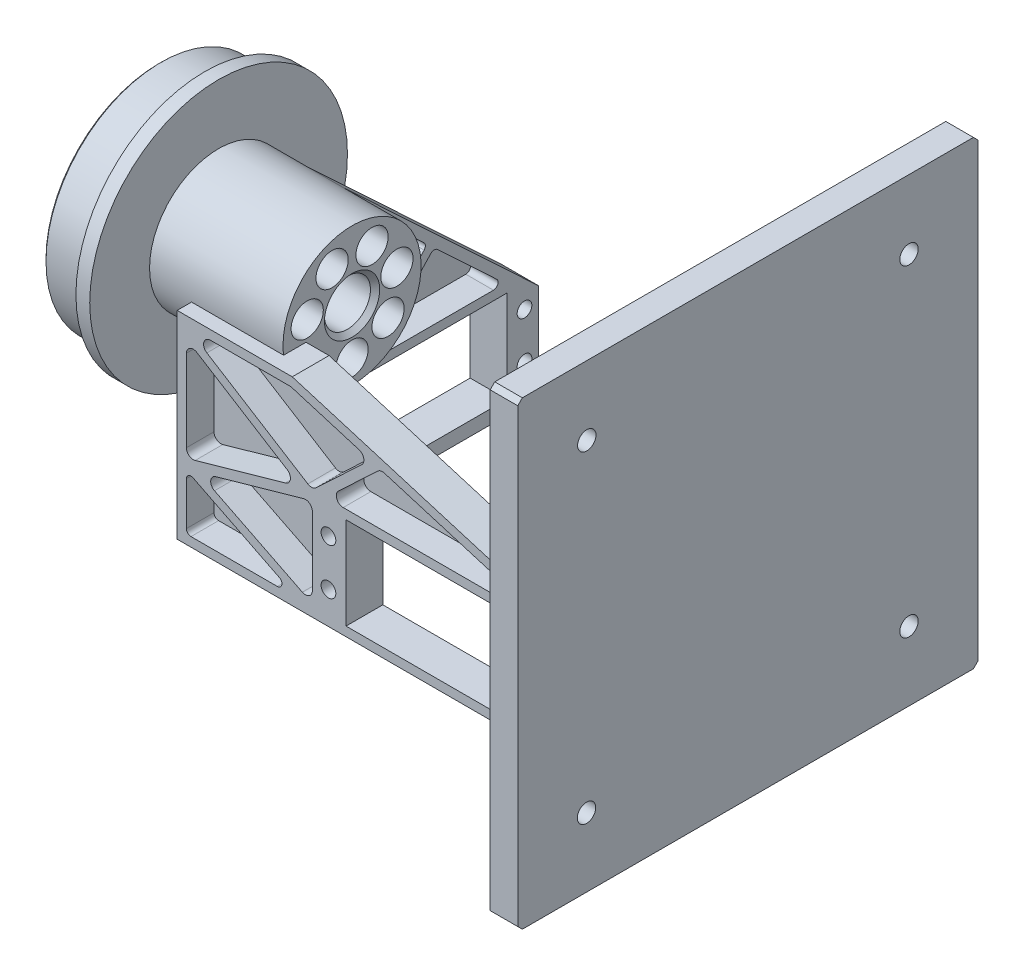
SolidWorks part; units mm, degrees
ref_plane "前视基准面" through (0, 0, 0) normal (0, 0, 1) x (1, 0, 0)
ref_plane "上视基准面" through (0, 0, 0) normal (0, 1, 0) x (1, 0, 0)
ref_plane "右视基准面" through (0, 0, 0) normal (1, 0, 0) x (0, 0, -1)
sketch "草图1" plane through (0, 0, 0) normal (0, 0, 1) x (1, 0, 0)
  line L0 (0, 42.2306) -> (0, 0) construction
  line L1 (0, 0) -> (67.1021, 0) construction
  line L2 (0, 28) -> (3, 28)
  line L3 (3, 28) -> (3, 25)
  line L4 (3, 25) -> (13, 25)
  line L5 (13, 25) -> (13, 28)
  line L6 (13, 28) -> (16, 28)
  line L7 (16, 28) -> (16, 15)
  line L8 (16, 15) -> (45, 15)
  line L9 (45, 15) -> (45, 5)
  line L10 (45, 5) -> (7.5, 5)
  line L11 (0, 12.5) -> (0, 28)
  line L12 (7.5, 5) -> (0, 12.5)
  dimension "D1" = 10
  dimension "D2" = 10
  dimension "D3" = 50
  dimension "D4" = 3
  dimension "D5" = 10
  dimension "D6" = 3
  dimension "D7" = 45
  dimension "D8" = 45
  dimension "D9" = 25
revolve "旋转1" add sketch "草图1" angle 360 about L1
ref_plane "基准面1" through (26, 0, 0) normal (1, 0, 0) x (0, 0, -1)
sketch "草图2" plane through (26, 0, 0) normal (1, 0, 0) x (0, 0, -1)
  line L0 (0, 0) -> (0, 50) construction
  line L1 (-13.9972, 50.28) -> (-14.997, 0.3)
  line L2 (13.9972, 50.28) -> (14.997, 0.3)
  circle A0 centre (0, 0) radius 5 construction
  circle A1 centre (0, 0) radius 5
  circle A2 centre (0, 0) radius 15 construction
  arc A3 (-14.997, 0.3) -> (14.997, 0.3) centre (0, 0) ccw
  circle A4 centre (0, 50) radius 6.5
  circle A5 centre (0, 50) radius 9.5 construction
  arc A6 (13.9972, 50.28) -> (-13.9972, 50.28) centre (0, 50) ccw
  circle A7 centre (0, 59.5) radius 1.5
  circle A8 centre (8.2272, 54.75) radius 1.5
  circle A9 centre (8.2272, 45.25) radius 1.5
  circle A10 centre (0, 40.5) radius 1.5
  circle A11 centre (-8.2272, 45.25) radius 1.5
  circle A12 centre (-8.2272, 54.75) radius 1.5
  point P26 (0, 50)
  dimension "D1" = 13
  dimension "D2" = 19
  dimension "D3" = 28
  dimension "D5" = 3
  dimension "D4" = 50
  dimension "D6" = 6
extrude "凸台-拉伸1" add sketch "草图2" along normal blind 8
sketch "草图3" plane through (34, 0, 0) normal (1, 0, 0) x (0, 0, -1)
  line L11 (13.4973, 0.27) -> (12.4975, 50.25)
  line L12 (13.3665, 6.807) -> (13.0385, 23.2073)
  line L13 (0, 15) -> (0, 50) construction
  line L14 (-12.4975, 50.25) -> (-13.4973, 0.27)
  line L15 (-12.6236, 43.9465) -> (-12.9969, 25.2871)
  line L16 (2.5, 14.7902) -> (12.9969, 25.2871)
  line L17 (13.0385, 23.2073) -> (4.2241, 14.393)
  line L18 (-2.5, 14.7902) -> (-12.9969, 25.2871)
  line L19 (-13.0385, 23.2073) -> (-4.2241, 14.393)
  line L20 (12.9969, 25.2871) -> (12.6236, 43.9465)
  line L21 (-13.0385, 23.2073) -> (-13.3665, 6.807)
  circle A10 centre (0, 50) radius 12.5
  arc A11 (14.997, 0.3) -> (-14.997, 0.3) centre (0, 0) ccw construction
  arc A12 (13.3665, 6.807) -> (4.2241, 14.393) centre (0, 0) ccw
  arc A13 (-12.6236, 43.9465) -> (12.6236, 43.9465) centre (0, 50) ccw
  arc A14 (13.9972, 50.28) -> (-13.9972, 50.28) centre (0, 50) ccw construction
  arc A15 (2.5, 14.7902) -> (-2.5, 14.7902) centre (0, 0) ccw
  arc A16 (-4.2241, 14.393) -> (-13.3665, 6.807) centre (0, 0) ccw
  dimension "D1" = 25
  dimension "D4" = 1.5
  dimension "D2" = 1.5
  dimension "D5" = 90
  dimension "D6" = 5
  dimension "D3" = 1.5
extrude "切除-拉伸1" cut sketch "草图3" against normal blind 6
fillet "圆角1" radius 1.5 12 edges at (31, 25.2871, -12.9969) (31, 43.9465, -12.6236) (31, 43.9465, 12.6236) (31, 14.7902, 2.5) (31, 14.393, 4.2241) (31, 23.2073, 13.0385) (31, 6.807, 13.3665) (31, 6.807, -13.3665) (31, 23.2073, -13.0385) (31, 14.393, -4.2241) (31, 14.7902, -2.5) (31, 25.2871, 12.9969)
sketch "草图4" plane through (45, 0, 0) normal (1, 0, 0) x (0, 0, -1)
  line L0 (-10, -1.9376) -> (-10, -45)
  line L1 (-10, -45) -> (-18, -45)
  line L2 (-18, -45) -> (-18, -1.9376)
  line L3 (-18, -1.9376) -> (-10, -1.9376)
  circle A0 centre (0, 0) radius 15 construction
  circle A2 centre (0, 0) radius 5 construction
  dimension "D1" = 10
  dimension "D2" = 45
  dimension "D3" = 8
extrude "凸台-拉伸2" add sketch "草图4" along normal blind 65 and the other way blind 20
sketch "草图5" plane through (0, 0, 18) normal (0, 0, 1) x (1, 0, 0)
  line L0 (0, 0) -> (152.7584, 0) construction
  line L1 (57.87, -38) -> (106.5, -38) construction
  line L2 (57.87, -38) -> (57.87, -28) construction
  line L3 (57.87, -28) -> (106.5, -28) construction
  line L4 (106.5, -38) -> (106.5, -28) construction
  line L5 (57.87, -38) -> (106.5, -28) construction
  line L6 (57.87, -28) -> (106.5, -38) construction
  line L8 (25, -45) -> (110, -45) construction
  line L9 (61.685, -43) -> (102.685, -43)
  line L10 (61.685, -43) -> (61.685, -23)
  line L11 (61.685, -23) -> (102.685, -23)
  line L12 (102.685, -43) -> (102.685, -23)
  line L13 (61.685, -43) -> (102.685, -23) construction
  line L14 (61.685, -23) -> (102.685, -43) construction
  line L15 (110, -1.9376) -> (110, -45) construction
  circle A0 centre (106.5, -28) radius 1.6
  circle A1 centre (106.5, -38) radius 1.6
  circle A2 centre (57.87, -28) radius 1.6
  circle A3 centre (57.87, -38) radius 1.6
  point P0 (82.185, -33)
  point P14 (82.185, -33)
  dimension "D3" = 3.2
  dimension "D5" = 3.5
  dimension "D1" = 10
  dimension "D2" = 48.63
  dimension "D4" = 12
  dimension "D6" = 20
  dimension "D7" = 41
extrude "切除-拉伸2" cut sketch "草图5" against normal through all
sketch "草图6" plane through (0, 0, 18) normal (0, 0, 1) x (1, 0, 0)
  line L0 (50, -1.9376) -> (110, -20)
  line L1 (25, -1.9376) -> (110, -1.9376) construction
  line L3 (110, -1.9376) -> (110, -45) construction
  line L4 (110, -20) -> (110, -1.9376)
  line L5 (110, -1.9376) -> (50, -1.9376)
  line L6 (25, -30) -> (55, -45)
  line L7 (25, -1.9376) -> (25, -45) construction
  line L8 (25, -45) -> (110, -45) construction
  line L9 (55, -45) -> (25, -45)
  line L10 (25, -45) -> (25, -30)
  dimension "D1" = 25
  dimension "D2" = 60
  dimension "D3" = 30
  dimension "D4" = 15
extrude "切除-拉伸3" cut sketch "草图6" against normal through all
sketch "草图7" plane through (0, 0, 18) normal (0, 0, 1) x (1, 0, 0)
  line L6 (106.3837, -21) -> (54.37, -21)
  line L7 (54.37, -21) -> (54.37, -42.4489)
  line L8 (102.685, -23) -> (61.685, -23) construction
  line L9 (49.7055, -3.9376) -> (27, -3.9376)
  line L10 (49.7055, -3.9376) -> (27, -3.9376)
  line L12 (108, -21.4866) -> (49.7055, -3.9376)
  line L14 (27, -3.9376) -> (27, -28.7639)
  line L15 (27, -28.7639) -> (55.4721, -43)
  line L16 (55.4721, -43) -> (108, -43)
  line L17 (108, -43) -> (108, -21.4866)
  line L18 (106.3837, -21) -> (49.7055, -3.9376)
  line L20 (27, -3.9376) -> (27, -28.7639)
  line L21 (27, -28.7639) -> (54.37, -42.4489)
  circle A0 centre (57.87, -28) radius 1.6 construction
  dimension "D2" = 3.5
  dimension "D3" = 2
  dimension "D1" = 2
extrude "切除-拉伸4" cut sketch "草图7" against normal blind 6
sketch "草图8" plane through (0, 0, 12) normal (0, 0, 1) x (1, 0, 0)
  line L0 (54.37, -21) -> (27, -3.9376) construction
  line L1 (54.37, -21) -> (27, -28.7639) construction
  line L2 (54.37, -21) -> (66.9811, -9.1383) construction
  line L3 (106.3837, -21) -> (49.7055, -3.9376) construction
  line L4 (66.9811, -9.1383) -> (54.37, -21)
  line L6 (54.37, -21) -> (106.3837, -21) construction
  line L7 (57.2891, -21) -> (69.1925, -9.804)
  line L8 (69.1925, -9.804) -> (66.9811, -9.1383)
  line L9 (54.37, -21) -> (27, -3.9376)
  line L10 (27, -3.9376) -> (27, -6.2944)
  line L11 (27, -3.9376) -> (27, -28.7639) construction
  line L12 (27, -6.2944) -> (51.7717, -21.737)
  line L15 (27, -28.7639) -> (51.7717, -21.737)
  line L17 (54.37, -42.4489) -> (54.37, -21) construction
  line L18 (54.37, -23.0789) -> (57.2891, -21)
  line L19 (27, -28.7639) -> (29.6528, -30.0903)
  line L20 (27, -28.7639) -> (54.37, -42.4489) construction
  line L21 (29.6528, -30.0903) -> (54.37, -23.0789)
  dimension "D1" = 60
  dimension "D2" = 2
  dimension "D3" = 2
  dimension "D4" = 2
extrude "凸台-拉伸3" add sketch "草图8" along normal up to surface (6 mm away) up to face at (53.1382, -20.1814, 18)
fillet "圆角2" radius 1.5 13 edges at (27, -6.2944, 15) (106.3837, -21, 15) (69.1925, -9.804, 15) (49.7055, -3.9376, 15) (27, -3.9376, 15) (54.37, -21, 15) (66.9811, -9.1383, 15) (54.37, -42.4489, 15) (57.2891, -21, 15) (27, -28.7639, 15) (51.7717, -21.737, 15) (29.6528, -30.0903, 15) (54.37, -23.0789, 15)
chamfer "倒角1" distance 5 angle 45 1 edges at (35, -11.1803, 10) first distance on face at (58.125, -20.7795, 10)
sketch "草图10" plane through (0, 0, 0) normal (-1, 0, 0) x (0, 0, 1)
  circle A0 centre (0, 0) radius 21 construction
  circle A1 centre (0, 21) radius 2.5
  circle A2 centre (18.1865, -10.5) radius 2.5
  circle A3 centre (-18.1865, -10.5) radius 2.5
  point P11 (0, 0)
  dimension "D1" = 42
  dimension "D2" = 5
  dimension "D3" = 3
extrude "切除-拉伸6" cut sketch "草图10" against normal blind 10
sketch "草图9" plane through (0, 0, 0) normal (-1, 0, 0) x (0, 0, 1)
  circle A0 centre (0, 0) radius 16
  circle A2 centre (0, 0) radius 28
  circle A3 centre (0, 0) radius 28
  dimension "D1" = 32
  dimension "D2" = 0
extrude "切除-拉伸5" cut sketch "草图9" against normal up to surface (3 mm away) up to face at (3, 0, 28)
chamfer "倒角2" distance 0.5 angle 45 5 edges at (0, 0, 16) (3, 0, 25) (3, -10.5, -15.6865) (3, -10.5, 20.6865) (3, 21, 2.5)
sketch "草图11" [suppressed] plane through (3, 0, 0) normal (-1, 0, 0) x (0, 0, 1)
  circle A0 centre (0, 0) radius 67.9276
extrude "切除-拉伸7" [suppressed] cut sketch "草图11" against normal through all
sketch "草图12" [suppressed] plane through (3, 0, 0) normal (1, 0, 0) x (0, 0, -1)
  circle A0 centre (0, 21) radius 2.5 construction
  circle A1 centre (0, 21) radius 2.5
  circle A2 centre (0, 21) radius 1.6
  circle A3 centre (18.1865, -10.5) radius 2.5
  circle A4 centre (18.1865, -10.5) radius 1.6
  circle A5 centre (-18.1865, -10.5) radius 2.5
  circle A6 centre (-18.1865, -10.5) radius 1.6
  point P12 (0, 0)
  dimension "D1" = 3.2
  dimension "D2" = 3
extrude "凸台-拉伸4" [suppressed] add sketch "草图12" against normal blind 3
sketch "草图13" [suppressed] plane through (3, 0, 0) normal (1, 0, 0) x (0, 0, -1)
  line L0 (0, 0) -> (0, 29.2927) construction
  arc A0 (-2.9985, 21.0938) -> (-2.462, 19.2857) centre (0, 21) ccw
  arc A1 (-2.462, 19.2857) -> (-3.1098, 17.7293) centre (-3.2826, 18.7143) cw
  arc A2 (15.4709, -11.775) -> (13.7991, -11.5579) centre (14.5657, -12.2) ccw
  circle A3 centre (0, 0) radius 22.5
  arc A4 (-4.184, 22.1076) -> (-21.2377, -7.4303) centre (0, 0) ccw
  arc A5 (2.462, 19.2857) -> (2.9985, 21.0938) centre (0, 21) ccw
  circle A6 centre (0, 0) radius 18
  arc A7 (-3.1098, 17.7293) -> (-16.909, -6.1715) centre (0, 0) ccw
  arc A8 (2.462, 19.2857) -> (3.1098, 17.7293) centre (3.2826, 18.7143) ccw
  arc A9 (15.4709, -11.775) -> (16.7685, -13.1437) centre (18.1865, -10.5) ccw
  arc A10 (19.767, -7.9501) -> (17.9329, -7.5107) centre (18.1865, -10.5) ccw
  arc A11 (17.9329, -7.5107) -> (16.909, -6.1715) centre (17.8484, -6.5143) cw
  arc A12 (-17.9329, -7.5107) -> (-16.909, -6.1715) centre (-17.8484, -6.5143) ccw
  arc A13 (-17.9329, -7.5107) -> (-19.767, -7.9501) centre (-18.1865, -10.5) ccw
  arc A14 (-16.7685, -13.1437) -> (-15.4709, -11.775) centre (-18.1865, -10.5) ccw
  arc A15 (-15.4709, -11.775) -> (-13.7991, -11.5579) centre (-14.5657, -12.2) cw
  arc A16 (16.909, -6.1715) -> (3.1098, 17.7293) centre (0, 0) ccw
  arc A17 (21.2377, -7.4303) -> (4.184, 22.1076) centre (0, 0) ccw
  arc A18 (-13.7991, -11.5579) -> (13.7991, -11.5579) centre (0, 0) ccw
  arc A19 (-17.0537, -14.6772) -> (17.0537, -14.6772) centre (0, 0) ccw
  arc A20 (4.184, 22.1076) -> (2.9985, 21.0938) centre (3.998, 21.125) ccw
  arc A21 (-4.184, 22.1076) -> (-2.9985, 21.0938) centre (-3.998, 21.125) cw
  arc A22 (21.2377, -7.4303) -> (19.767, -7.9501) centre (20.2938, -7.1001) cw
  arc A23 (17.0537, -14.6772) -> (16.7685, -13.1437) centre (16.2958, -14.0249) ccw
  arc A24 (-17.0537, -14.6772) -> (-16.7685, -13.1437) centre (-16.2958, -14.0249) cw
  arc A25 (-21.2377, -7.4303) -> (-19.767, -7.9501) centre (-20.2938, -7.1001) ccw
  point P41 (0, 0)
  point P56 (0, 0)
  dimension "D1" = 6
  dimension "D5" = 2
  dimension "D4" = 3
  dimension "D2" = 5
  dimension "D3" = 2
  dimension "D6" = 3
extrude "切除-拉伸8" [suppressed] cut sketch "草图13" against normal blind 1.5
chamfer "倒角3" [suppressed] distance 0.5 angle 45
sketch "草图14" plane through (3, 0, 0) normal (-1, 0, 0) x (0, 0, 1)
  line L0 (14.3565, 13.1962) -> (0, 0) construction
  line L1 (0, 0) -> (7.4345, 18.0272) construction
  line L2 (18.1865, -10.5) -> (0, 21) construction
  line L3 (0, 0) -> (9.0933, 5.25) construction
  arc A0 (7.4345, 18.0272) -> (14.3565, 13.1962) centre (0, 0) cw construction
  arc A1 (16.9333, 15.5648) -> (8.7689, 21.2628) centre (0, 0) ccw
  arc A2 (11.7797, 10.8277) -> (6.1001, 14.7915) centre (0, 0) ccw
  arc A3 (11.7797, 10.8277) -> (16.9333, 15.5648) centre (14.3565, 13.1962) ccw
  arc A4 (8.7689, 21.2628) -> (6.1001, 14.7915) centre (7.4345, 18.0272) ccw
  arc A5 (19.3292, -2.5751) -> (18.6065, 5.835) centre (0, 0) ccw construction
  arc A6 (21.9462, 6.8823) -> (22.7986, -3.0374) centre (0, 0) cw
  arc A7 (15.2669, 4.7877) -> (15.8599, -2.1129) centre (0, 0) cw
  arc A8 (15.2669, 4.7877) -> (21.9462, 6.8823) centre (18.6065, 5.835) cw
  arc A9 (22.7986, -3.0374) -> (15.8599, -2.1129) centre (19.3292, -2.5751) cw
  arc A10 (3.4872, -15.6154) -> (9.7598, -12.6786) centre (0, 0) ccw
  arc A11 (3.4872, -15.6154) -> (5.0128, -22.4471) centre (4.25, -19.0312) ccw
  arc A12 (14.0297, -18.2255) -> (9.7598, -12.6786) centre (11.8948, -15.452) ccw
  arc A13 (5.0128, -22.4471) -> (14.0297, -18.2255) centre (0, 0) ccw
  arc A14 (-5.0128, -22.4471) -> (-14.0297, -18.2255) centre (0, 0) cw
  arc A15 (-14.0297, -18.2255) -> (-9.7598, -12.6786) centre (-11.8948, -15.452) cw
  arc A16 (-3.4872, -15.6154) -> (-9.7598, -12.6786) centre (0, 0) cw
  arc A17 (-3.4872, -15.6154) -> (-5.0128, -22.4471) centre (-4.25, -19.0312) cw
  arc A18 (11.8948, -15.452) -> (4.25, -19.0312) centre (0, 0) cw construction
  arc A19 (-11.8948, -15.452) -> (-4.25, -19.0312) centre (0, 0) ccw construction
  arc A20 (-15.2669, 4.7877) -> (-15.8599, -2.1129) centre (0, 0) ccw
  arc A21 (-15.2669, 4.7877) -> (-21.9462, 6.8823) centre (-18.6065, 5.835) ccw
  arc A22 (-22.7986, -3.0374) -> (-15.8599, -2.1129) centre (-19.3292, -2.5751) ccw
  arc A23 (-21.9462, 6.8823) -> (-22.7986, -3.0374) centre (0, 0) ccw
  arc A24 (-16.9333, 15.5648) -> (-8.7689, 21.2628) centre (0, 0) cw
  arc A25 (-8.7689, 21.2628) -> (-6.1001, 14.7915) centre (-7.4345, 18.0272) cw
  arc A26 (-11.7797, 10.8277) -> (-6.1001, 14.7915) centre (0, 0) cw
  arc A27 (-11.7797, 10.8277) -> (-16.9333, 15.5648) centre (-14.3565, 13.1962) cw
  arc A28 (-19.3292, -2.5751) -> (-18.6065, 5.835) centre (0, 0) cw construction
  arc A29 (-7.4345, 18.0272) -> (-14.3565, 13.1962) centre (0, 0) ccw construction
  point P4 (11.16, 15.9907)
  point P20 (19.4284, 1.6695)
  point P29 (8.2684, -17.6602)
  point P36 (-8.2684, -17.6602)
  point P43 (-19.4284, 1.6695)
  point P50 (-11.16, 15.9907)
  point P55 (0, 0)
  dimension "D1" = 3.5
  dimension "D4" = 8.5
  dimension "D2" = 19.5
  dimension "D3" = 25
  dimension "D5" = 3
extrude "切除-拉伸9" cut sketch "草图14" against normal up to surface (10 mm away) up to face at (13, 0, 25)
sketch "草图15" plane through (45, 0, 0) normal (1, 0, 0) x (0, 0, -1)
  line L0 (14.997, 0.3) -> (13.9972, 50.28) construction
  line L1 (-13.9972, 50.28) -> (-14.997, 0.3) construction
  line L2 (14.997, 0.3) -> (13.9972, 50.28)
  line L3 (-13.9972, 50.28) -> (-14.997, 0.3)
  arc A0 (14.997, 0.3) -> (-14.997, 0.3) centre (0, 0) ccw
  arc A1 (13.9972, 50.28) -> (-13.9972, 50.28) centre (0, 50) ccw construction
  arc A2 (13.9972, 50.28) -> (-13.9972, 50.28) centre (0, 50) ccw
  arc A3 (-7.0563, -13.2366) -> (-14.8743, -1.9376) centre (0, 0) ccw construction
extrude "切除-拉伸10" cut sketch "草图15" against normal up to surface (19 mm away) up to face at (26, 54.75, 6.7272)
sketch "草图16" plane through (0, 0, 18) normal (0, 0, 1) x (1, 0, 0)
  line L0 (25, -30) -> (27, -31)
  line L1 (55, -45) -> (25, -30) construction
  line L2 (27, -31) -> (27, -43)
  line L3 (27, -43) -> (51, -43)
  line L4 (51, -43) -> (55, -45)
  line L5 (55, -45) -> (25, -45)
  line L6 (25, -45) -> (25, -30)
  line L7 (27, -8.9971) -> (27, -26.7793) construction
  dimension "D1" = 2
extrude "凸台-拉伸5" add sketch "草图16" against normal up to surface (8 mm away) up to face at (58.125, -22.0295, 10)
sketch "草图17" plane through (0, 0, 10) normal (0, 0, -1) x (-1, 0, 0)
  line L0 (-27, -43) -> (-27, -31) construction
  line L1 (-51, -43) -> (-27, -43) construction
  line L2 (-27, -31) -> (-51, -43) construction
  line L3 (-27, -43) -> (-27, -31)
  line L4 (-51, -43) -> (-27, -43)
  line L5 (-27, -31) -> (-51, -43)
extrude "凸台-拉伸6" add sketch "草图17" against normal up to surface (2 mm away) up to face at (34.9607, -19.0424, 12)
fillet "圆角4" radius 1 3 edges at (27, -43, 15) (51, -43, 15) (27, -31, 15)
sketch "草图18" plane through (25, 0, 0) normal (-1, 0, 0) x (0, 0, 1)
  line L0 (10, -45) -> (10, -16.1803) construction
  line L1 (7.0563, -13.2366) -> (10, -16.1803) construction
  line L2 (10, -45) -> (10, -16.1803)
  line L3 (7.0563, -13.2366) -> (10, -16.1803)
  line L5 (-52.4658, -44.5) -> (-52.4658, -28.5)
  line L6 (-52.4658, -28.5) -> (-10.2417, 10.9593)
  line L7 (-49.4658, -36.5) -> (-32.3158, -36.5) construction
  line L8 (-49.4658, -31.5) -> (-0.8358, -31.5) construction
  line L9 (-49.4658, -31.5) -> (-49.4658, -41.5) construction
  line L10 (-49.4658, -41.5) -> (-0.8358, -41.5) construction
  line L11 (-0.8358, -31.5) -> (-0.8358, -41.5) construction
  line L12 (-49.4658, -31.5) -> (-0.8358, -41.5) construction
  line L13 (-49.4658, -41.5) -> (-0.8358, -31.5) construction
  line L14 (10, -45) -> (18, -45)
  line L15 (-45.6508, -46.5) -> (-4.6508, -46.5)
  line L16 (-45.6508, -46.5) -> (-45.6508, -26.5)
  line L17 (-45.6508, -26.5) -> (-4.6508, -26.5)
  line L18 (-4.6508, -46.5) -> (-4.6508, -26.5)
  line L19 (-45.6508, -46.5) -> (-4.6508, -26.5) construction
  line L20 (-45.6508, -26.5) -> (-4.6508, -46.5) construction
  line L21 (18, -45) -> (13.5, -49.5)
  line L22 (13.5, -49.5) -> (-47.4658, -49.5)
  line L23 (-47.4658, -49.5) -> (-52.4658, -44.5)
  arc A0 (14.8743, -1.9376) -> (7.0563, -13.2366) centre (0, 0) ccw construction
  arc A1 (-10.2417, 10.9593) -> (7.0563, -13.2366) centre (0, 0) ccw
  circle A2 centre (-49.4658, -31.5) radius 1.6
  circle A3 centre (-49.4658, -41.5) radius 1.6
  circle A4 centre (-0.8358, -31.5) radius 1.6
  circle A5 centre (-0.8358, -41.5) radius 1.6
  circle A6 centre (0, 0) radius 48.75 construction
  point P8 (-25.1508, -36.5)
  point P18 (-25.1508, -36.5)
  point P28 (-52.4658, -49.5)
  dimension "D3" = 3
  dimension "D4" = 3.2
  dimension "D5" = 3
  dimension "D7" = 97.5
  dimension "D1" = 10
  dimension "D2" = 48.63
  dimension "D6" = 17.15
  dimension "D8" = 20
  dimension "D9" = 41
  dimension "D10" = 3
  dimension "D11" = 36.5
  dimension "D12" = 45
extrude "凸台-拉伸7" add sketch "草图18" against normal blind 8
sketch "草图19" plane through (33, 0, 0) normal (1, 0, 0) x (0, 0, -1)
  line L9 (-2.1642, -47.5) -> (-2.1642, -24.5)
  line L10 (-2.1642, -24.5) -> (45.2564, -24.5)
  line L11 (4.6508, -26.5) -> (45.6508, -26.5) construction
  line L14 (-10, -16.1803) -> (-10, -47.5)
  line L15 (16.8797, 2.0186) -> (14.3436, 4.3886)
  line L16 (-8, -47) -> (-13.1716, -47)
  line L17 (-13.1716, -47) -> (-12.6716, -47.5)
  line L18 (-12.6716, -47.5) -> (46.6374, -47.5)
  line L19 (46.6374, -47.5) -> (50.4658, -43.6716)
  line L20 (50.4658, -43.6716) -> (50.4658, -29.3684)
  line L21 (50.4658, -29.3684) -> (16.8797, 2.0186)
  line L22 (-6.6406, -15.6494) -> (-8, -17.0088)
  line L23 (-8, -17.0088) -> (-8, -47)
  line L26 (-10, -47.5) -> (-2.1642, -47.5)
  line L29 (45.2564, -24.5) -> (16.8797, 2.0186)
  line L33 (-10, -16.1803) -> (-7.0563, -13.2366) construction
  line L34 (-10, -16.1803) -> (-7.0563, -13.2366)
  circle A1 centre (0.8358, -31.5) radius 1.6 construction
  arc A2 (-6.6406, -15.6494) -> (16.8797, 2.0186) centre (0, 0) ccw
  arc A4 (-7.0563, -13.2366) -> (-14.8743, -1.9376) centre (0, 0) ccw construction
  arc A5 (-7.0563, -13.2366) -> (10.2417, 10.9593) centre (0, 0) ccw construction
  arc A6 (-7.0563, -13.2366) -> (14.3436, 4.3886) centre (0, 0) ccw
  dimension "D2" = 2
  dimension "D3" = 3
  dimension "D1" = 2
extrude "切除-拉伸11" cut sketch "草图19" against normal blind 6
sketch "草图20" plane through (33, 0, 0) normal (1, 0, 0) x (0, 0, -1)
  line L0 (0, -15) -> (0, -24.5)
  line L1 (-2.1642, -24.5) -> (45.2564, -24.5) construction
  line L2 (0, -24.5) -> (3, -24.5)
  line L3 (-2.1642, -24.5) -> (45.2564, -24.5) construction
  line L4 (3, -24.5) -> (3, -14.6969)
  line L5 (13.5641, -24.5) -> (28.3388, -8.6901)
  line L6 (45.2564, -24.5) -> (14.3436, 4.3886) construction
  line L7 (28.3388, -8.6901) -> (29.8, -10.0557)
  line L8 (45.2564, -24.5) -> (14.3436, 4.3886) construction
  line L9 (29.8, -10.0557) -> (16.3015, -24.5)
  line L10 (16.3015, -24.5) -> (13.5641, -24.5)
  arc A2 (0, -15) -> (3, -14.6969) centre (0, 0) ccw
  arc A3 (-7.0563, -13.2366) -> (14.3436, 4.3886) centre (0, 0) ccw construction
  arc A4 (-7.0563, -13.2366) -> (-14.8743, -1.9376) centre (0, 0) ccw construction
  dimension "D1" = 3
  dimension "D2" = 2
extrude "凸台-拉伸8" add sketch "草图20" against normal up to surface (6 mm away) up to face at (27, -25.169, -4.8726)
fillet "圆角5" radius 1 13 edges at (30, -47.5, 2.1642) (30, -47.5, 10) (30, 4.3886, -14.3436) (30, -24.5, -45.2564) (30, -24.5, 2.1642) (30, -15, 0) (30, -14.6969, -3) (30, -24.5, -3) (30, -24.5, 0) (30, -24.5, -16.3015) (30, -24.5, -13.5641) (30, -8.6901, -28.3388) (30, -10.0557, -29.8)
fillet "圆角6" radius 3 1 edges at (33, -45, 14)
chamfer "倒角4" distance 1 angle 45 1 edges at (45, 0, 5)
sketch "草图21" plane through (45, 0, 0) normal (1, 0, 0) x (0, 0, -1)
  line L0 (-5, -8.6603) -> (0, 0) construction
  line L1 (0, 0) -> (0, -10) construction
  circle A0 centre (0, 0) radius 10 construction
  circle A2 centre (0, -10) radius 3.5
  circle A3 centre (-7.8183, -6.2349) radius 3.5 construction
  circle A4 centre (-9.7493, 2.2252) radius 3.5
  circle A5 centre (-4.3388, 9.0097) radius 3.5
  circle A6 centre (4.3388, 9.0097) radius 3.5
  circle A7 centre (9.7493, 2.2252) radius 3.5
  circle A8 centre (7.8183, -6.2349) radius 3.5
  point P21 (0, 0)
  dimension "D1" = 20
  dimension "D2" = 7
  dimension "D3" = 30
  dimension "D4" = 7
extrude "切除-拉伸12" cut sketch "草图21" against normal blind 35
sketch "草图22" plane through (110, 0, 0) normal (1, 0, 0) x (0, 0, -1)
  line L4 (-18, -20) -> (-18, -45)
  line L5 (-10, -20) -> (-18, -20)
  line L6 (-10, -45) -> (-10, -20)
  line L7 (-10, -20) -> (-18, -20)
  line L8 (-18, -20) -> (-18, -45)
  line L10 (-10, -45) -> (-10, -20)
  line L12 (-18, -45) -> (-10, -45)
  line L13 (-18, -45) -> (-10, -45)
  dimension "D1" = 0
extrude "凸台-拉伸9" add sketch "草图22" along normal blind 20
sketch "草图24" plane through (130, 0, 0) normal (1, 0, 0) x (0, 0, -1)
  line L5 (-50, 50.1147) -> (50, 50.1147)
  line L6 (-50, 50.1147) -> (-50, -49.8853)
  line L7 (-50, -49.8853) -> (50, -49.8853)
  line L8 (50, 50.1147) -> (50, -49.8853)
  line L9 (-50, 50.1147) -> (50, -49.8853) construction
  line L10 (-50, -49.8853) -> (50, 50.1147) construction
  circle A0 centre (-35.0574, -34.9426) radius 2
  circle A1 centre (-35, 35.1147) radius 2
  circle A2 centre (35, 35.1147) radius 2
  circle A3 centre (35, -34.8853) radius 2
  dimension "D3" = 100
  dimension "D1" = 15
other "对齐组1" parameters "D2"=4, "D5"=4, "D1"=118.2033, "D3"=42.596, "D4"=100
extrude "凸台-拉伸11" add sketch "草图24" along normal blind 1 and the other way blind 5
chamfer "倒角7" distance 1 angle 45 4 edges at (128, -49.8853, 50) (128, -49.8853, -50) (128, 50.1147, -50) (128, 50.1147, 50)
chamfer "倒角8" distance 2 angle 45 4 edges at (125, -20, 14) (125, -32.5, 18) (125, -45, 14) (125, -32.5, 10)
sketch "草图25" plane through (131, 0, 0) normal (1, 0, 0) x (0, 0, -1)
  line L8 (-49, -49.8853) -> (49, -49.8853)
  line L9 (-50, -48.8853) -> (-49, -49.8853)
  line L10 (50, -48.8853) -> (50, 49.1147)
  line L11 (-50, -48.8853) -> (-49, -49.8853)
  line L12 (49, 50.1147) -> (-49, 50.1147)
  line L13 (49, -49.8853) -> (50, -48.8853)
  line L14 (-50, 49.1147) -> (-50, -48.8853)
  line L15 (49, -49.8853) -> (50, -48.8853)
  line L16 (-49, -49.8853) -> (49, -49.8853)
  line L18 (50, -48.8853) -> (50, 49.1147)
  line L20 (49, 50.1147) -> (-49, 50.1147)
  line L22 (-50, 49.1147) -> (-50, -48.8853)
  line L24 (50, 49.1147) -> (49, 50.1147)
  line L25 (50, 49.1147) -> (49, 50.1147)
  line L26 (-49, 50.1147) -> (-50, 49.1147)
  line L27 (-49, 50.1147) -> (-50, 49.1147)
  dimension "D1" = 0
